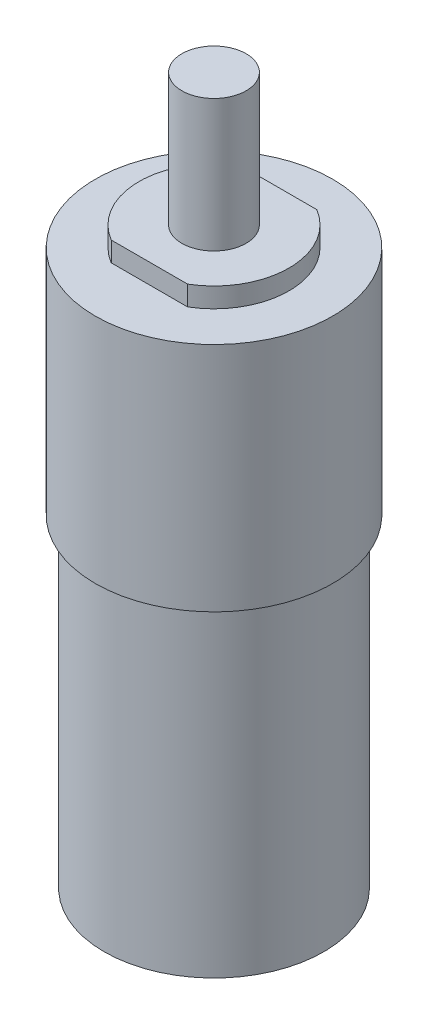
SolidWorks part; units mm, degrees
ref_plane "Front Plane" through (0, 0, 0) normal (0, 0, 1) x (1, 0, 0)
ref_plane "Top Plane" through (0, 0, 0) normal (0, 1, 0) x (1, 0, 0)
ref_plane "Right Plane" through (0, 0, 0) normal (1, 0, 0) x (0, 0, -1)
sketch "Sketch1" plane through (0, 0, 0) normal (0, 1, 0) x (1, 0, 0)
  circle A0 centre (0, 0) radius 10.16
  dimension "D1" = 20.32
extrude "Boss-Extrude1" add sketch "Sketch1" along normal blind 29.8958
sketch "Sketch2" plane through (0, 29.8958, 0) normal (0, 1, 0) x (1, 0, 0)
  circle A0 centre (0, 0) radius 10.9728
  dimension "D1" = 21.9456
extrude "Boss-Extrude2" add sketch "Sketch2" along normal blind 21.4122
sketch "Sketch3" plane through (0, 51.308, 0) normal (0, 1, 0) x (1, 0, 0)
  circle A0 centre (0, 0) radius 6.9342
  dimension "D1" = 13.8684
extrude "Boss-Extrude3" add sketch "Sketch3" along normal blind 1.8288
sketch "Sketch4" plane through (0, 53.1368, 0) normal (0, 1, 0) x (1, 0, 0)
  circle A0 centre (0, 0) radius 2.9718
  dimension "D1" = 5.9436
extrude "Boss-Extrude4" add sketch "Sketch4" along normal blind 65.3542 from surface starting at face at (0, 0, 10.16)
sketch "Sketch5" plane through (0, 53.1368, 0) normal (0, 1, 0) x (1, 0, 0)
  line L0 (-3.529, 5.969) -> (3.529, 5.969)
  line L2 (3.529, -5.969) -> (-3.529, -5.969)
  arc A0 (-3.529, -5.969) -> (3.529, -5.969) centre (0, 0) ccw
  arc A2 (3.529, 5.969) -> (-3.529, 5.969) centre (0, 0) ccw
  circle A3 centre (0, 0) radius 6.9342 construction
  dimension "D1" = 11.938
extrude "Cut-Extrude1" cut sketch "Sketch5" against normal up to surface (1.8288 mm away) up to face at (0, 51.308, 6.9342)
